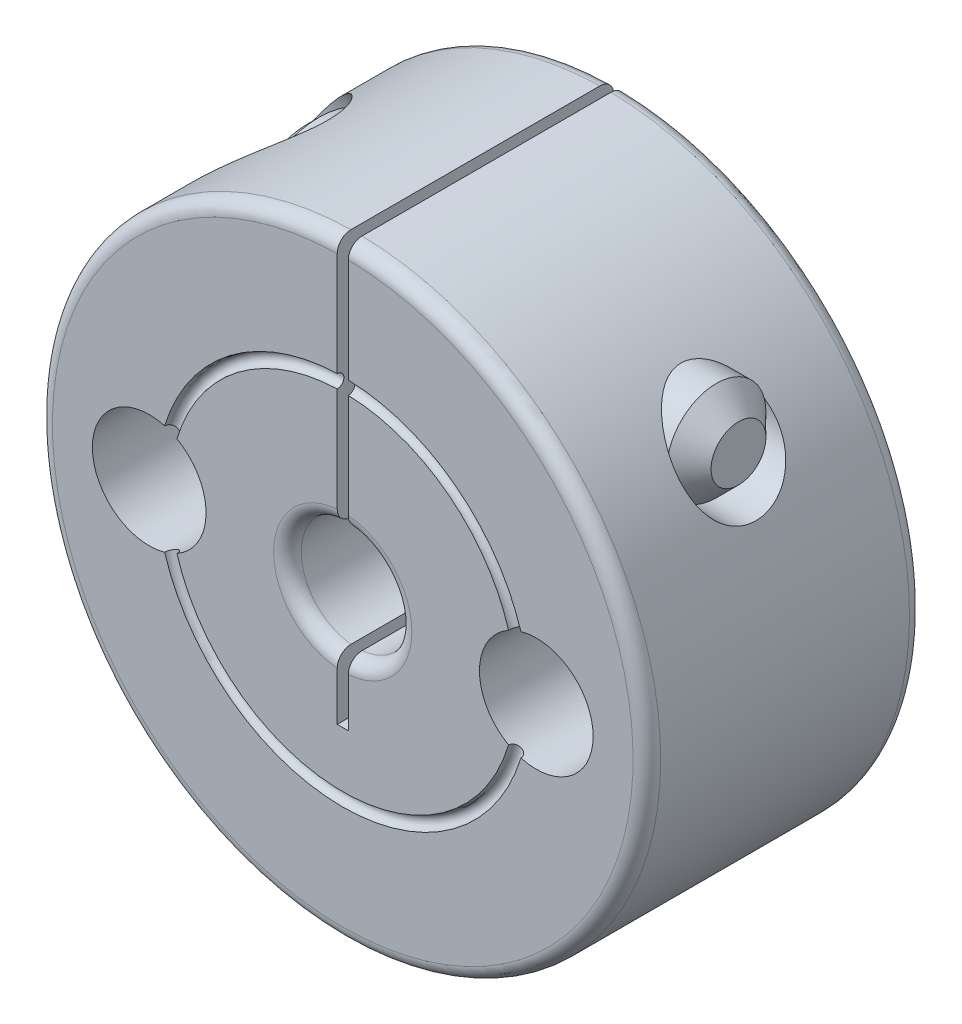
SolidWorks part; units mm, degrees
ref_plane "Front Plane" through (0, 0, 0) normal (0, 0, 1) x (1, 0, 0)
ref_plane "Top Plane" through (0, 0, 0) normal (0, 1, 0) x (1, 0, 0)
ref_plane "Right Plane" through (0, 0, 0) normal (1, 0, 0) x (0, 0, -1)
sketch "Sketch1" plane through (0, 0, 0) normal (0, 0, 1) x (1, 0, 0)
  line L0 (-0.1588, 1.5795) -> (-0.1588, 8.7298)
  line L2 (0.1588, 1.5795) -> (0.1588, 8.7298)
  line L3 (0, 0) -> (0, 1.5795) construction
  line L4 (0.1588, 1.5795) -> (-0.1588, 1.5795) construction
  line L5 (0, -8.7312) -> (0, -1.5875) construction
  line L6 (0, -1.5875) -> (0, -5.1594) construction
  line L7 (-0.1588, -1.5795) -> (-0.1588, -3.3734)
  line L8 (-0.1588, -3.3734) -> (0.1587, -3.3734)
  line L9 (0.1588, -1.5795) -> (0.1587, -3.3734)
  line L10 (-0.1588, 5.1547) -> (0.1587, 5.1547) construction
  circle A0 centre (0, 0) radius 8.7312 construction
  circle A1 centre (0, 0) radius 1.5875 construction
  arc A3 (-0.1588, 8.7298) -> (0.1588, 8.7298) centre (0, 0) ccw
  arc A4 (0.1588, -1.5795) -> (0.1588, 1.5795) centre (0, 0) ccw
  arc A5 (-0.1588, 1.5795) -> (-0.1588, -1.5795) centre (0, 0) ccw
  point P4 (8.7312, 0)
  point P5 (-8.7312, 0)
  point P19 (0, -3.3734)
  dimension "Bore Dia" = 3.175
  dimension "OD" = 17.4625
  dimension "Separation" = 0.3175
extrude "Extrude1" add sketch "Sketch1" along normal mid plane 7.9375
fillet "Fillet1" radius 0.3969 6 edges at (0, -8.7312, -3.9688) (0, -8.7312, 3.9688) (-1.5875, 0, 3.9688) (-1.5875, 0, -3.9688) (1.5875, 0, 3.9688) (1.5875, 0, -3.9688)
sketch "Sketch2" plane through (0, 0, 0) normal (0, 1, 0) x (1, 0, 0)
  line L0 (0, 0) -> (-1.5875, 0) construction
  line L1 (-1.5875, 0) -> (-8.7312, 0) construction
  line L2 (-5.1594, 3.9688) -> (-5.1594, -3.9688) construction
  line L3 (8.3344, 3.9688) -> (-8.3344, 3.9688) construction
  line L4 (-8.3344, -3.9688) -> (8.3344, -3.9688) construction
  line L5 (-8.7312, 3.5719) -> (-8.7312, -3.5719) construction
  line L6 (-1.5875, 3.5719) -> (-1.5875, -3.5719) construction
  line L8 (-5.3499, -3.9688) -> (-4.9689, -3.9688)
  line L9 (0, 3.9688) -> (0, -3.9688) construction
  line L10 (-0.1588, 3.9688) -> (-1.9844, 3.9688) construction
  arc A1 (-4.9689, -3.9688) -> (-5.3499, -3.9688) centre (-5.1594, -3.9688) ccw
  point P1 (-5.1594, 0)
  dimension "D2" = 0.1905
revolve "Cut-Revolve1" cut sketch "Sketch2" angle 360 about L9
sketch "Sketch3" plane through (0, 0, 0) normal (0, 0, 1) x (1, 0, 0)
  line L0 (8.7312, 5.1547) -> (-8.7312, 5.1547)
  line L1 (-8.7312, 5.1547) -> (-8.7313, 2.7671)
  line L2 (-8.7313, 2.7671) -> (-2.1336, 2.7671)
  line L4 (-2.1336, 2.7671) -> (-2.1336, 3.7323)
  line L7 (-2.1336, 3.7323) -> (8.7313, 3.7323)
  line L8 (8.7313, 3.7323) -> (8.7312, 5.1547)
  line L9 (-8.7312, 5.1547) -> (-11.1189, 5.1547) construction
  line L10 (-0.1588, 5.1547) -> (0.1587, 5.1547) construction
  dimension "D4" = 4.7752
  dimension "D2" = 2.1336
revolve "Cut-Revolve2" cut sketch "Sketch3" angle 360 about L9
sketch "Sketch4" plane through (0, 0, 0) normal (0, 0, 1) x (1, 0, 0)
  line L0 (-4.9784, 5.1547) -> (-4.9784, 7.4788)
  line L2 (-4.9784, 7.4788) -> (-2.1336, 7.4788)
  line L3 (-2.1336, 7.4788) -> (-2.1336, 6.5771)
  line L4 (-2.1336, 6.5771) -> (7.3914, 6.5771)
  line L5 (-2.1336, 2.7671) -> (-2.1336, 3.7323) construction
  line L6 (7.3914, 6.5771) -> (7.3914, 5.1547)
  line L7 (-2.1336, 3.7323) -> (8.7313, 3.7323) construction
  line L8 (7.3914, 5.1547) -> (-4.9784, 5.1547)
  line L9 (7.3914, 6.5771) -> (7.3914, 3.7323) construction
  line L10 (-4.9784, 5.1547) -> (-7.3025, 5.1547) construction
  line L11 (-8.7312, 5.1547) -> (-11.1189, 5.1547) construction
  dimension "Head Dia" = 4.6482
revolve "Revolve1" add sketch "Sketch4" angle 360 about L8
sketch "Sketch5" plane through (-4.9784, 0, 0) normal (-1, 0, 0) x (0, -1, 0)
  line L1 (-4.4673, -1.1906) -> (-3.7799, 0)
  line L2 (-3.7799, 0) -> (-4.4673, 1.1906)
  line L3 (-4.4673, 1.1906) -> (-5.8421, 1.1906)
  line L4 (-5.8421, 1.1906) -> (-6.5295, 0)
  line L5 (-6.5295, 0) -> (-5.8421, -1.1906)
  line L6 (-5.8421, -1.1906) -> (-4.4673, -1.1906)
  circle A0 centre (-5.1547, 0) radius 1.1906 construction
  dimension "Hex" = 2.3813
extrude "Cut-Extrude1" cut sketch "Sketch5" against normal blind 2.3813
chamfer "Chamfer1" distance 0.3175 angle 45 1 edges at (-4.9784, 7.4788, 0)
sketch "Sketch6" plane through (7.3914, 0, 0) normal (1, 0, 0) x (0, 1, 0)
  circle A0 centre (5.1547, 0) radius 1.4224 construction
  circle A1 centre (5.1547, 0) radius 1.4224
  point P3 (6.5771, 0)
curve "Helix/Spiral1" [suppressed] pitch 0.635 height 9.525 turns 15 parameters "Height"=9.525, "Pitch"=0.635
sketch "Sketch7" plane through (0, 0, 0) normal (0, 0, 1) x (1, 0, 0)
  line L0 (7.6692, 6.0959) -> (7.3517, 6.6458) construction
  line L1 (7.3517, 6.6458) -> (7.9867, 6.6458) construction
  line L2 (7.9867, 6.6458) -> (7.6692, 6.0959) construction
  line L3 (7.3914, 6.5771) -> (7.947, 6.5771) construction
  line L4 (7.6295, 6.1646) -> (7.7089, 6.1646)
  line L5 (7.6692, 6.6458) -> (7.6692, 6.5771) construction
  line L6 (7.6692, 6.1646) -> (7.6692, 6.0959) construction
  line L7 (7.6295, 6.1646) -> (7.3716, 6.6114)
  line L8 (7.3716, 6.6114) -> (7.9669, 6.6114)
  line L9 (7.9669, 6.6114) -> (7.7089, 6.1646)
  point P10 (7.6692, 6.6114)
  dimension "D1" = 0.635
  dimension "D2" = 0.0794
chamfer "Chamfer2" distance 0.635 angle 45 1 edges at (7.3914, 6.5771, 0)
sweep "Cut-Sweep1" [suppressed] cut profiles "Sketch7" path "Helix/Spiral1"
hole_wizard "#4 Clearance Hole2" positions "Sketch9" profile "Sketch10" hole size "#4" standard "ANSI Inch" end condition up to next
sketch "Sketch9" plane through (0, 0, -3.9688) normal (0, 0, -1) x (-1, 0, 0)
  circle A0 centre (0, 0) radius 5.5562 construction
  point P4 (-5.5562, 0)
  point P6 (5.5562, 0)
  dimension "D1" = 11.1125
sketch "Sketch10" plane through (-5.5562, 0, -3.9688) normal (1, 0, 0) x (0, 1, 0)
  line L0 (0, 0) -> (0, 7.9375)
  line L1 (0, 7.9375) -> (1.6319, 7.9375)
  line L2 (1.6319, 7.9375) -> (1.6319, 0)
  line L5 (1.6319, 0) -> (0, 0)
  line L11 (0, -6.35) -> (0, 107.95) construction
  dimension "Thru Hole Dia." = 3.2639
  dimension "Thru Hole Depth" = 7.9375
equation "\"D1@Sketch3\" = \"Screw Dia@Sketch3\""
equation "\"D1@Cut-Extrude1\" = \"Hex@Sketch5\""
equation "\"D1@Fillet1\" = \"Width@Extrude1\"*.05"
equation "\"D4@Sketch3\" = \"Head Dia@Sketch4\" + .005"
equation "\"Height@Helix/Spiral1\" = \"Screw Lg@Sketch4\""
equation "\"D1@Sketch7\" = \"Pitch@Helix/Spiral1\""
equation "\"D2@Sketch7\" = \"D1@Sketch7\"/8"
equation "\"D1@Chamfer2\" = \"Pitch@Helix/Spiral1\""
equation "\"Separation@Sketch1\" = \"Bore Dia@Sketch1\"/10"
equation "\"D2@Sketch3\" = \"Screw Dia@Sketch3\"*.750"
